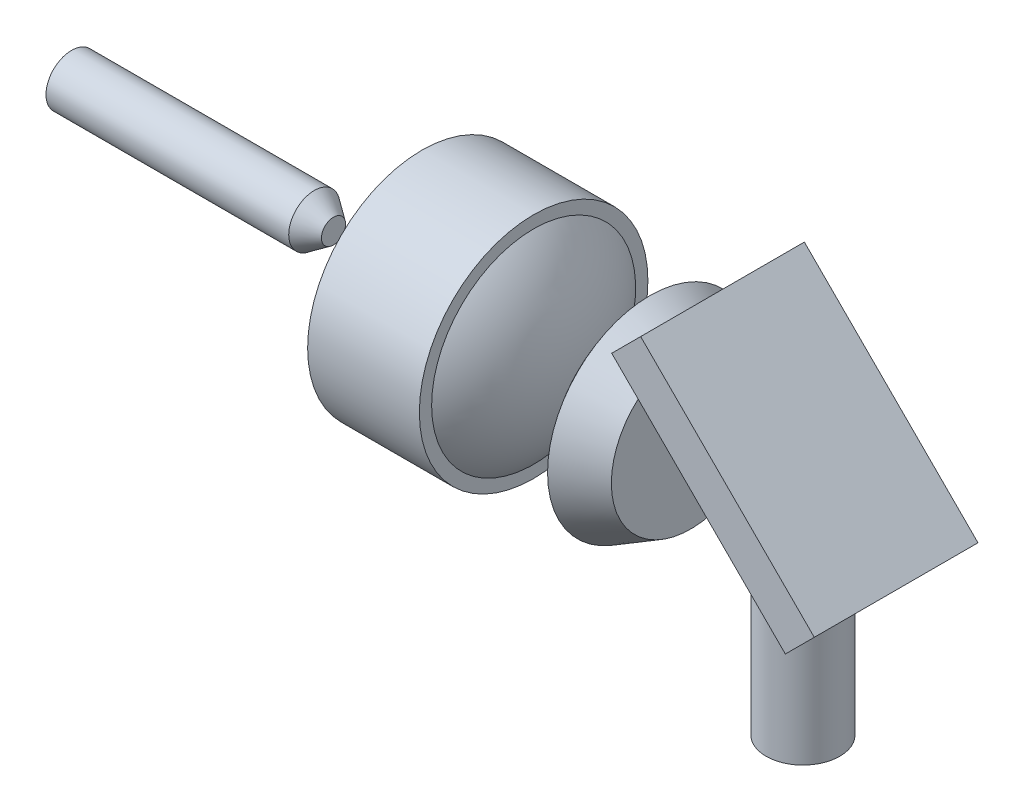
SolidWorks part; units mm, degrees
ref_plane "Front Plane" through (0, 0, 0) normal (0, 0, 1) x (1, 0, 0)
ref_plane "Top Plane" through (0, 0, 0) normal (0, 1, 0) x (1, 0, 0)
ref_plane "Right Plane" through (0, 0, 0) normal (1, 0, 0) x (0, 0, -1)
sketch "Sketch1" plane through (0, 0, 0) normal (0, 0, 1) x (1, 0, 0)
  line L0 (0, 0) -> (1, 0) construction
  line L1 (18.87, 0) -> (18.87, -1) construction
  line L2 (20.4407, -1.4293) -> (16.1981, 2.8134)
  line L4 (16.1981, 2.8134) -> (16.9052, 3.5205)
  line L5 (21.1478, -0.7222) -> (16.9052, 3.5205)
  line L6 (20.4407, -1.4293) -> (21.1478, -0.7222)
  line L7 (7.4, 0.625) -> (9.56, 0.625) construction
  line L8 (19.77, -1) -> (17.97, -1)
  line L10 (19.77, -4.93) -> (17.97, -4.93)
  line L11 (17.97, -1) -> (17.97, -4.93)
  line L13 (16.13, -2.5) -> (16.13, 2.5)
  line L14 (16.13, 2.5) -> (14.26, 2.5) construction
  line L15 (14.26, 0) -> (14.26, 2.5) construction
  line L18 (12.29, 2.7925) -> (9.56, 2.7925)
  line L19 (9.56, -2.7925) -> (9.56, 2.7925)
  line L21 (7.4, -0.625) -> (7.4, 0.625)
  line L22 (7.4, 0.625) -> (1, 0.625)
  line L23 (1, -0.625) -> (1, 0.625)
  line L24 (13.26, -0.9848) -> (13.26, 0) construction
  line L25 (16.13, 2.5) -> (15.13, 2.5)
  line L26 (12.29, 2.7925) -> (12.29, 2.4925)
  line L27 (14.26, -0.9848) -> (14.26, 0) construction
  line L28 (16.13, -2.5) -> (15.13, -2.5)
  line L29 (12.29, -2.7925) -> (9.56, -2.7925)
  line L30 (12.29, -2.7925) -> (12.29, -2.4925)
  line L31 (7.4, -0.625) -> (1, -0.625)
  line L32 (16.13, 0) -> (18.87, 0) construction
  line L33 (13.26, 0) -> (14.26, 0) construction
  line L34 (7.4, 0) -> (9.56, 0) construction
  line L35 (19.77, -1) -> (19.77, -4.93)
  line L36 (18.87, -4.93) -> (18.87, -38.5877) construction
  line L37 (1, 0) -> (7.4, 0)
  line L38 (9.56, 0) -> (13.26, 0)
  line L39 (14.26, 0) -> (16.13, 0)
  line L40 (18.87, -1) -> (18.87, -4.93)
  line L41 (6.9306, 0.625) -> (7.4, 0.2946)
  line L42 (0, -2) -> (1, -2) construction
  line L43 (1, -2) -> (7.4, -2) construction
  line L44 (7.4, -2) -> (42.8776, -2) construction
  line L45 (18.87, -1) -> (18.87, 0.1414) construction
  line L46 (20.37, -1.5) -> (16.0566, 2.8134)
  line L47 (16.0566, 2.8134) -> (16.9052, 3.6619)
  line L48 (21.2185, -0.6515) -> (16.9052, 3.6619)
  line L50 (20.4407, -1.4293) -> (20.37, -1.5)
  line L51 (21.1478, -0.7222) -> (21.2185, -0.6515)
  line L52 (21.2892, -0.7222) -> (16.9052, 3.6619) construction
  line L53 (20.4407, -1.5707) -> (21.2892, -0.7222) construction
  line L54 (20.4407, -1.5707) -> (16.0566, 2.8134) construction
  line L55 (21.87, -1) -> (21.87, -4.93) construction
  line L56 (15.13, 2.5) -> (18.87, 0.4088)
  line L57 (18.87, 0.4088) -> (19.77, -1)
  line L58 (18.9019, 0.3589) -> (21.2185, -1.4293)
  line L59 (21.2185, -1.4293) -> (18.9019, 0.3589)
  arc A0 (12.29, 2.4925) -> (12.29, -2.4925) centre (9.5727, 0) cw
  arc A1 (15.13, -2.5) -> (15.13, 2.5) centre (18.287, 0) cw
  point P33 (13.26, -0.4924)
  point P35 (14.26, -0.4924)
  point P47 (18.87, 0)
  dimension "D2" = 6.4
  dimension "D3" = 2.16
  dimension "D5" = 1.87
  dimension "D10" = 0.3
  dimension "D9" = 2.73
  dimension "D11" = 1
  dimension "D4" = 6
  dimension "D6" = 1
  dimension "D7" = 0.9
  dimension "D8" = 3.93
  dimension "D12" = 0.625
  dimension "D13" = 2.7925
  dimension "D14" = 2.5
  dimension "D15" = 0.97
  dimension "D17" = 1
  dimension "D18" = 0.4694
  dimension "D19" = 1
  dimension "D23" = 45
  dimension "D22" = 2
  dimension "D21" = 0.5
  dimension "D25" = 2.74
  dimension "D26" = 1
  dimension "D27" = 6.57
  dimension "D20" = 2
  dimension "D16" = 0.1
  dimension "D24" = 3
extrude "Boss-Extrude1" add sketch "Sketch1" along normal mid plane 4 contours L6 L5 L4 L2
revolve "Revolve4" add sketch "Sketch1<6>" angle 360 about L0 region at (15.2763, 1.0506, 0) region at (11.2392, 1.3171, 0) region at (4.1398, 0.3085, 0)
sketch "Sketch1<6>" plane through (0, 0, 0) normal (0, 0, 1) x (1, 0, 0) same geometry as "Sketch1"
revolve "Revolve5" add sketch "Sketch1<7>" angle 360 about L40 region at (18.42, -2.965, 0)
sketch "Sketch1<7>" plane through (0, 0, 0) normal (0, 0, 1) x (1, 0, 0) same geometry as "Sketch1"
equation "\"b\"= 3.74 - \"D25@Sketch1\""
equation "\"D17@Sketch1\"=\"b\""
